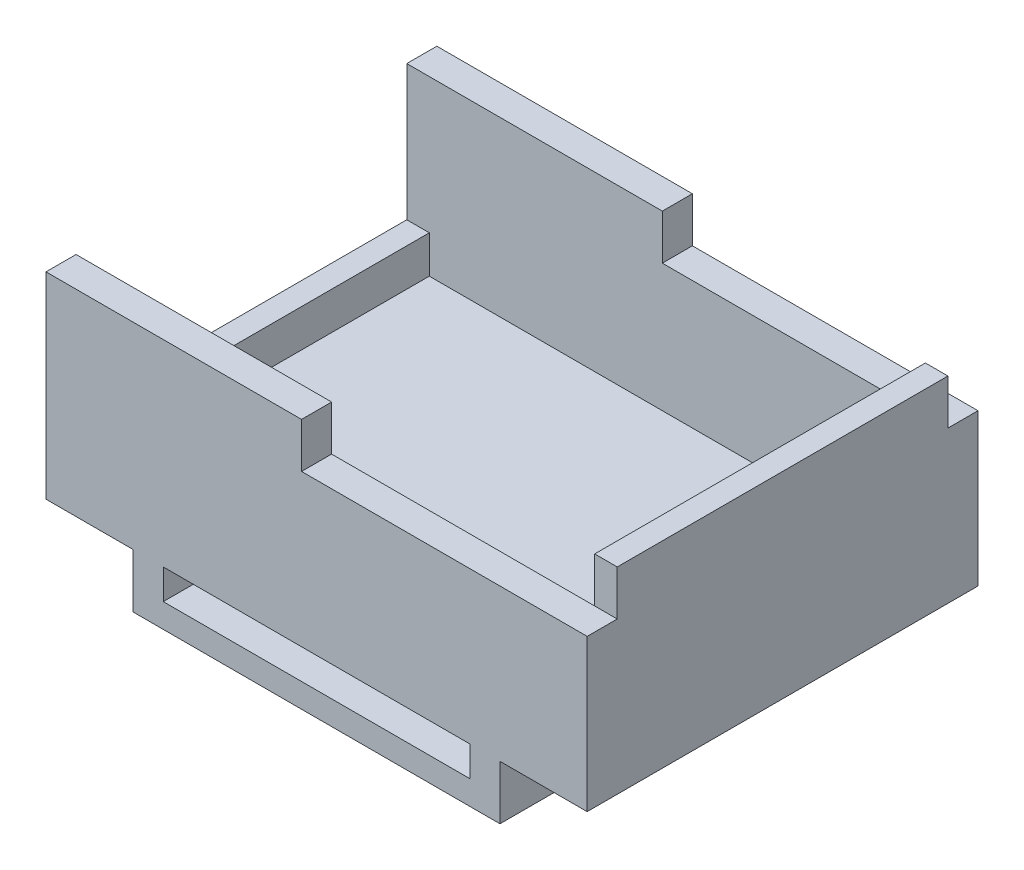
SolidWorks part; units mm, degrees
ref_plane "前视基准面" through (0, 0, 0) normal (0, 0, 1) x (1, 0, 0)
ref_plane "上视基准面" through (0, 0, 0) normal (0, 1, 0) x (1, 0, 0)
ref_plane "右视基准面" through (0, 0, 0) normal (1, 0, 0) x (0, 0, -1)
sketch "草图1" plane through (0, 0, 0) normal (0, 1, 0) x (1, 0, 0)
  line L1 (-18, 13) -> (18, 13)
  line L2 (-18, 13) -> (-18, -13)
  line L3 (-18, -13) -> (18, -13)
  line L4 (18, 13) -> (18, -13)
  line L5 (-18, 13) -> (18, -13) construction
  line L6 (-18, -13) -> (18, 13) construction
  point P0 (0, 0)
extrude "凸台-拉伸1" add sketch "草图1" along normal blind 14.6
sketch "草图2" plane through (0, 14.6, 0) normal (0, 1, 0) x (1, 0, 0)
  line L1 (-16.5, 11) -> (16.5, 11)
  line L2 (-16.5, 11) -> (-16.5, -11)
  line L3 (-16.5, -11) -> (16.5, -11)
  line L4 (16.5, 11) -> (16.5, -11)
  line L5 (-16.5, 11) -> (16.5, -11) construction
  line L6 (-16.5, -11) -> (16.5, 11) construction
  point P0 (0, 0)
extrude "切除-拉伸1" cut sketch "草图2" against normal blind 13
sketch "草图3" plane through (0, 14.6, 0) normal (0, 1, 0) x (1, 0, 0)
  line L1 (-18, 13) -> (18, 13)
  line L2 (-18, 13) -> (-18, -13)
  line L3 (-18, -13) -> (18, -13)
  line L4 (18, 13) -> (18, -13)
extrude "切除-拉伸2" cut sketch "草图3" against normal blind 4.5
sketch "草图4" plane through (0, 10.1, 0) normal (0, 1, 0) x (1, 0, 0)
  line L0 (-18, 13) -> (-18, -13) construction
  line L1 (-16.5, 11) -> (-18, 11)
  line L2 (-16.5, 11) -> (-16.5, -11)
  line L3 (-16.5, -11) -> (-18, -11)
  line L4 (-18, 11) -> (-18, -11)
extrude "切除-拉伸3" cut sketch "草图4" against normal blind 6
sketch "草图5" plane through (0, 0, 0) normal (0, -1, 0) x (-1, 0, 0)
  line L0 (0, 0) -> (0, -13) construction
  line L1 (0, -13) -> (10.2, -13) construction
  line L2 (18, -13) -> (-18, -13) construction
  line L3 (-10.2, -9) -> (-12.2, -9)
  line L4 (10.2, -13) -> (12.2, -13)
  line L5 (10.2, -13) -> (10.2, -9)
  line L6 (10.2, -9) -> (12.2, -9)
  line L7 (12.2, -13) -> (12.2, -9)
  line L8 (-12.2, -13) -> (-12.2, -9)
  line L9 (-10.2, -13) -> (-12.2, -13)
  line L10 (-10.2, -13) -> (-10.2, -9)
  line L11 (0, 0) -> (-2, 0) construction
  line L12 (-10.2, 13) -> (-10.2, 9)
  line L13 (-10.2, 13) -> (-12.2, 13)
  line L14 (-12.2, 13) -> (-12.2, 9)
  line L15 (-10.2, 9) -> (-12.2, 9)
  line L16 (10.2, 9) -> (12.2, 9)
  line L17 (12.2, 13) -> (12.2, 9)
  line L18 (10.2, 13) -> (12.2, 13)
  line L19 (10.2, 13) -> (10.2, 9)
extrude "凸台-拉伸2" add sketch "草图5" along normal blind 2
sketch "草图6" plane through (0, -2, 0) normal (0, -1, 0) x (-1, 0, 0)
  line L1 (12.2, -13) -> (-12.2, -13)
  line L2 (12.2, -13) -> (12.2, -9)
  line L3 (12.2, -9) -> (-12.2, -9)
  line L4 (-12.2, -13) -> (-12.2, -9)
  line L5 (12.2, 9) -> (-12.2, 9)
  line L6 (12.2, 9) -> (12.2, 13)
  line L7 (12.2, 13) -> (-12.2, 13)
  line L8 (-12.2, 9) -> (-12.2, 13)
extrude "凸台-拉伸3" add sketch "草图6" along normal blind 1.6
sketch "草图7" plane through (0, 10.1, 0) normal (0, 1, 0) x (1, 0, 0)
  line L0 (16.5, 11) -> (-16.5, 11) construction
  line L1 (-18, 13) -> (-1, 13)
  line L2 (-18, 13) -> (-18, 11)
  line L3 (-18, 11) -> (-1, 11)
  line L4 (-1, 13) -> (-1, 11)
  line L5 (-18, -13) -> (18, -13) construction
  line L6 (-18, -11) -> (-1, -11)
  line L7 (-18, -11) -> (-18, -13)
  line L8 (-18, -13) -> (-1, -13)
  line L9 (-1, -11) -> (-1, -13)
  line L10 (18, -13) -> (18, 13) construction
  line L11 (16.5, -11) -> (18, -11)
  line L12 (16.5, -11) -> (16.5, 11)
  line L13 (16.5, 11) -> (18, 11)
  line L14 (18, -11) -> (18, 11)
extrude "凸台-拉伸4" add sketch "草图7" along normal blind 3
